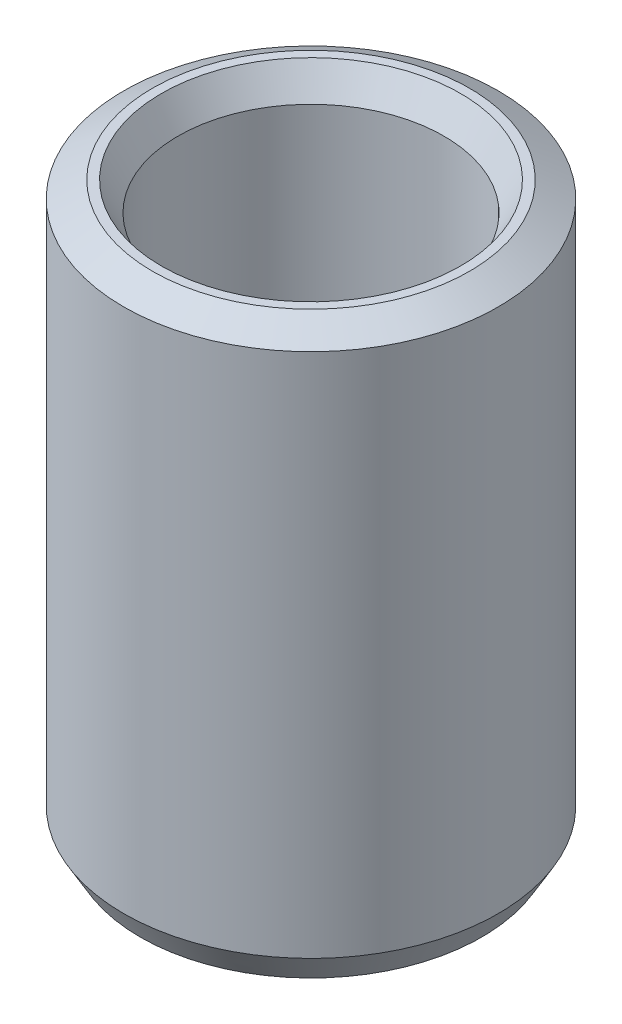
SolidWorks part; units mm, degrees
ref_plane "Front Plane" through (0, 0, 0) normal (0, 0, 1) x (1, 0, 0)
ref_plane "Top Plane" through (0, 0, 0) normal (0, 1, 0) x (1, 0, 0)
ref_plane "Right Plane" through (0, 0, 0) normal (1, 0, 0) x (0, 0, -1)
sketch "Sketch1" plane through (0, 0, 0) normal (0, 1, 0) x (1, 0, 0)
  circle A0 centre (0, 0) radius 25
  dimension "SLEEVE_OD" = 50
extrude "Boss-Extrude1" add sketch "Sketch1" along normal blind 76.1938
sketch "Sketch2" plane through (0, 0, 0) normal (0, 1, 0) x (1, 0, 0)
  circle A0 centre (0, 0) radius 17.7569
  dimension "BORE_D" = 35.5137
extrude "Cut-Extrude1" cut sketch "Sketch2" along normal through all
chamfer "Chamfer1" distance 2.2097 angle 60 4 edges at (0, 76.1938, 17.7569) (0, 0, 17.7569) (0, 0, 25) (0, 76.1938, 25) first distance on face at (0, 76.1938, 17.7569) first distance on face at (0, 0, 17.7569) first distance on face at (0, 76.1938, 25)
